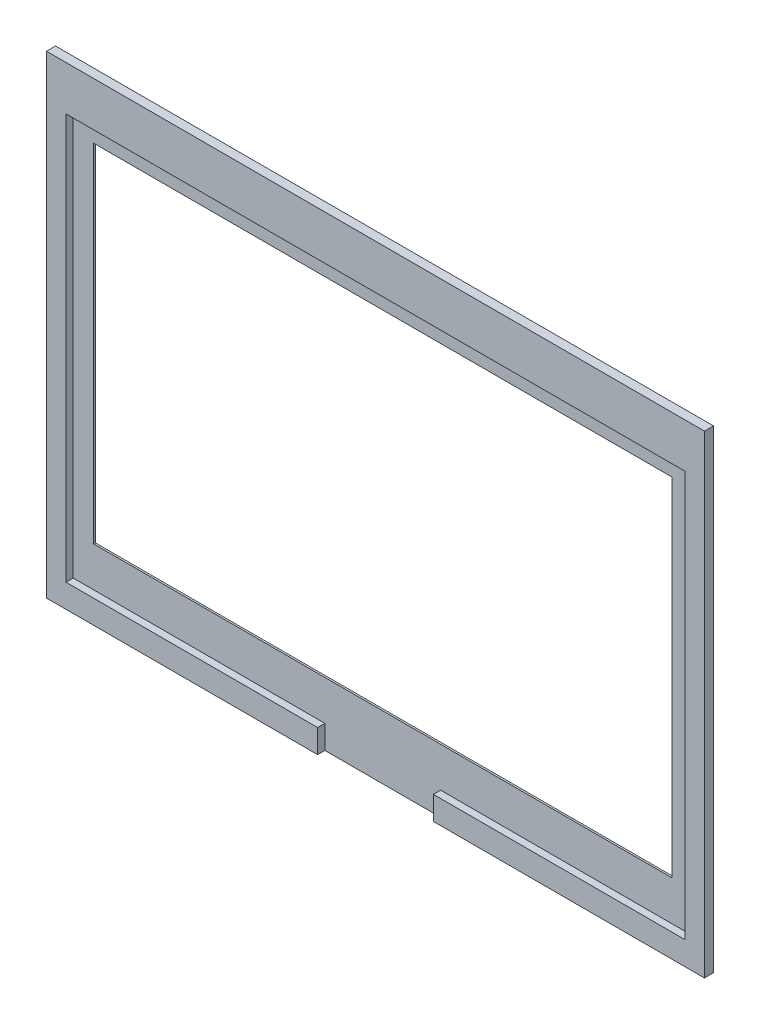
SolidWorks part; units mm, degrees
ref_plane "Plano frontal" through (0, 0, 0) normal (0, 0, 1) x (1, 0, 0)
ref_plane "Plano superior" through (0, 0, 0) normal (0, 1, 0) x (1, 0, 0)
ref_plane "Plano direito" through (0, 0, 0) normal (1, 0, 0) x (0, 0, -1)
sketch "Esboço1" plane through (0, 0, 0) normal (0, 0, 1) x (1, 0, 0)
  line L0 (11, 65.5) -> (171, 65.5) construction
  line L1 (0, 0) -> (182, 0)
  line L2 (0, 0) -> (0, 131)
  line L3 (0, 131) -> (182, 131)
  line L4 (182, 0) -> (182, 131)
  line L5 (11, 113.5) -> (171, 113.5)
  line L6 (11, 113.5) -> (11, 17.5)
  line L7 (11, 17.5) -> (171, 17.5)
  line L8 (171, 113.5) -> (171, 17.5)
  line L9 (5.4, 118.7) -> (176.6, 118.7)
  line L10 (5.4, 118.7) -> (5.4, 6.5)
  line L11 (5.4, 6.5) -> (176.6, 6.5)
  line L12 (176.6, 118.7) -> (176.6, 6.5)
  line L13 (5.9, 118.2) -> (176.1, 118.2) construction
  line L14 (5.9, 118.2) -> (5.9, 7) construction
  line L15 (5.9, 7) -> (176.1, 7) construction
  line L16 (176.1, 118.2) -> (176.1, 7) construction
  line L17 (91, 131) -> (91, 0) construction
  point P21 (91, 65.5)
  point P22 (91, 65.5)
  dimension "D1" = 131
  dimension "D2" = 182
  dimension "D3" = 160
  dimension "D4" = 96
  dimension "D5" = 170.2
  dimension "D6" = 111.2
  dimension "D7" = 0.5
  dimension "D8" = 4.7
  dimension "D9" = 0.5
  dimension "D10" = 0.5
  dimension "D11" = 0.5
  dimension "D12" = 5.1
  dimension "D13" = 5.1
  dimension "D14" = 10.5
extrude "Ressalto-extrusão1" add sketch "Esboço1" along normal blind 2.5 contours L1 L4 L3 L2 L9 L12 L11 L10 region at (2.2424, 65.5, 0)
extrude "Ressalto-extrusão2" add sketch "Esboço1<4>" along normal blind 0.5 contours L12 L9 L10 L11 L5 L8 L7 L6 region at (91, 116.6531, 0)
sketch "Esboço1<4>" plane through (0, 0, 0) normal (0, 0, 1) x (1, 0, 0) same geometry as "Esboço1"
sketch "Esboço2" plane through (0, 6.5, 0) normal (0, 1, 0) x (1, 0, 0)
  line L0 (5.4, -0.5) -> (176.6, -0.5) construction
  line L1 (75, -0.5) -> (107, -0.5)
  line L2 (75, -0.5) -> (75, -31.1981)
  line L3 (75, -31.1981) -> (107, -31.1981)
  line L4 (107, -0.5) -> (107, -31.1981)
  point P6 (91, -0.5)
  point P7 (91, -0.5)
  dimension "D1" = 32
extrude "Corte-extrusão1" cut sketch "Esboço2" against normal through all
